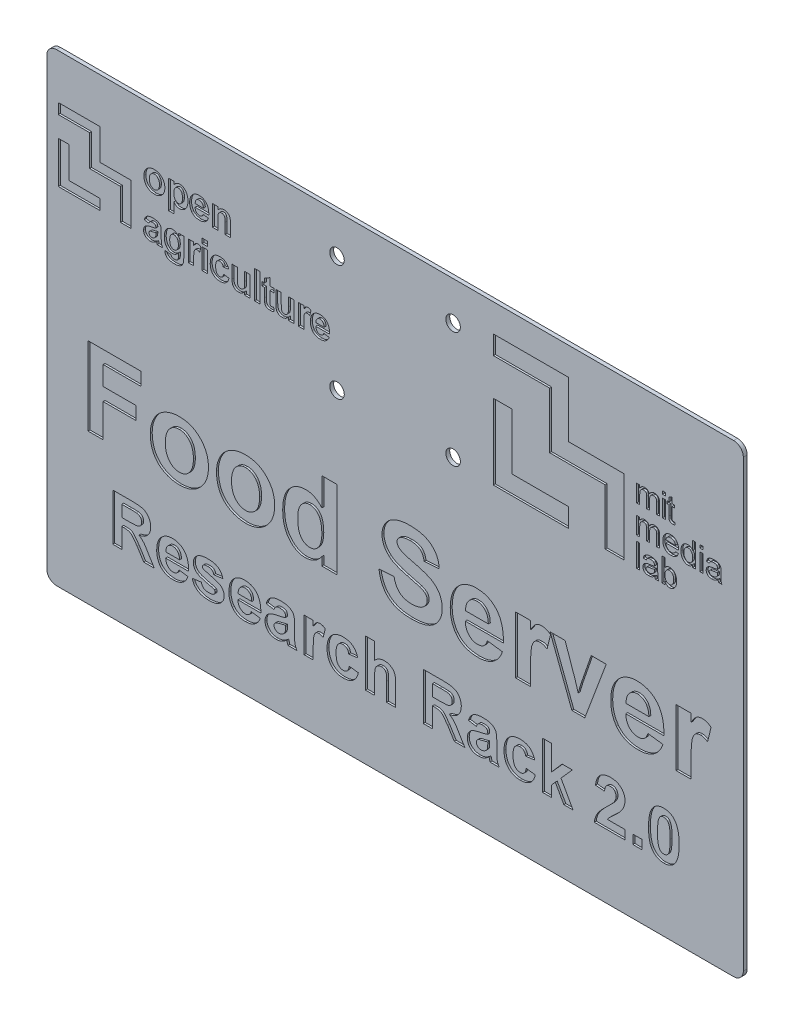
SolidWorks part; units mm, degrees
ref_plane "Front" through (0, 0, 0) normal (0, 0, 1) x (1, 0, 0)
ref_plane "Top" through (0, 0, 0) normal (0, 1, 0) x (1, 0, 0)
ref_plane "Right" through (0, 0, 0) normal (1, 0, 0) x (0, 0, -1)
sketch "Sketch1" plane through (0, 0, 0) normal (0, 0, 1) x (1, 0, 0)
  line L0 (0, 0) -> (0, 88.9) construction
  line L1 (-228.6, 152.4) -> (228.6, 152.4)
  line L2 (-228.6, 152.4) -> (-228.6, -152.4)
  line L3 (-228.6, -152.4) -> (228.6, -152.4)
  line L4 (228.6, 152.4) -> (228.6, -152.4)
  line L5 (-228.6, 152.4) -> (228.6, -152.4) construction
  line L6 (-228.6, -152.4) -> (228.6, 152.4) construction
  line L8 (-38.1, 127) -> (38.1, 127) construction
  line L9 (-38.1, 127) -> (-38.1, 50.8) construction
  line L10 (-38.1, 50.8) -> (38.1, 50.8) construction
  line L11 (38.1, 127) -> (38.1, 50.8) construction
  line L12 (-38.1, 127) -> (38.1, 50.8) construction
  line L13 (-38.1, 50.8) -> (38.1, 127) construction
  circle A0 centre (38.1, 127) radius 4.7625
  circle A1 centre (38.1, 50.8) radius 4.7625
  circle A2 centre (-38.1, 50.8) radius 4.7625
  circle A3 centre (-38.1, 127) radius 4.7625
  point P0 (0, 0)
  point P16 (0, 85.676)
  dimension "D3" = 9.525
  dimension "D1" = 457.2
  dimension "D2" = 304.8
  dimension "D4" = 76.2
  dimension "D5" = 76.2
  dimension "D6" = 25.4
extrude "Boss-Extrude1" add sketch "Sketch1" along normal blind 2.54
sketch "Sketch2" plane through (0, 0, 2.54) normal (0, 0, 1) x (1, 0, 0)
  line L0 (-228.6, -110.3412) -> (228.6, -110.3412) construction
  line L1 (-228.6, 152.4) -> (-228.6, -152.4) construction
  line L2 (228.6, -152.4) -> (228.6, 152.4) construction
  line L3 (-228.6, -54.1215) -> (228.6, -54.1215) construction
  line L4 (0, 0) -> (0, 83.06) construction
  line L6 (64.5155, 134.119) -> (113.7506, 134.119)
  line L7 (113.7506, 134.119) -> (113.7506, 97.5418)
  line L8 (113.7506, 97.5418) -> (150.2405, 97.5418)
  line L9 (150.2405, 97.5418) -> (150.2405, 48.5217)
  line L10 (150.2405, 48.5217) -> (137.9317, 48.5217)
  line L11 (137.9317, 48.5217) -> (137.9317, 85.0584)
  line L12 (137.9317, 85.0584) -> (101.5292, 85.0584)
  line L13 (101.5292, 85.0584) -> (101.5292, 121.8102)
  line L14 (101.5292, 121.8102) -> (64.5155, 121.8102)
  line L15 (64.5155, 121.8102) -> (64.5155, 134.119)
  line L16 (64.5155, 97.5418) -> (76.9116, 97.5418)
  line L17 (76.9116, 97.5418) -> (76.9116, 60.6155)
  line L18 (76.9116, 60.6155) -> (113.7506, 60.6155)
  line L19 (113.7506, 60.6155) -> (113.7506, 48.2194)
  line L20 (113.7506, 48.2194) -> (64.5155, 48.2194)
  line L21 (64.5155, 48.2194) -> (64.5155, 97.5418)
  line L22 (157.2149, 85.0584) -> (225.8164, 85.0584) construction
  line L23 (157.2149, 66.7596) -> (220.6979, 66.7596) construction
  line L24 (157.2149, 47.8869) -> (195.1273, 47.8869) construction
  line L25 (-221.0468, 122.883) -> (-193.694, 122.883)
  line L26 (-193.694, 122.883) -> (-193.694, 102.5624)
  line L27 (-193.694, 102.5624) -> (-173.4218, 102.5624)
  line L28 (-173.4218, 102.5624) -> (-173.4218, 75.161)
  line L29 (-173.4218, 75.161) -> (-180.2601, 75.161)
  line L30 (-180.2601, 75.161) -> (-180.2601, 95.6272)
  line L31 (-180.2601, 95.6272) -> (-200.4837, 95.6272)
  line L32 (-200.4837, 95.6272) -> (-200.4837, 116.0448)
  line L33 (-200.4837, 116.0448) -> (-221.0468, 116.0448)
  line L34 (-221.0468, 116.0448) -> (-221.0468, 122.883)
  line L35 (-221.0468, 102.5624) -> (-214.1601, 102.5624)
  line L36 (-214.1601, 102.5624) -> (-214.1601, 82.0478)
  line L37 (-214.1601, 82.0478) -> (-193.694, 82.0478)
  line L38 (-193.694, 82.0478) -> (-193.694, 75.161)
  line L39 (-193.694, 75.161) -> (-221.0468, 75.161)
  line L40 (-221.0468, 75.161) -> (-221.0468, 102.5624)
  line L41 (-165.808, 102.5624) -> (-74.3812, 102.5624) construction
  line L42 (-165.808, 74.527) -> (0.0083, 74.527) construction
  text T0 "mit" font "Arial" height in points 60
  text T1 "media" font "Arial" height in points 60
  text T2 "lab" font "Arial" height in points 60
  text T3 "open" font "Arial" height in points 72
  text T4 "agriculture" font "Arial" height in points 72
  text T5 "Food Server" font "Arial" height in points 200
  text T6 "Research Rack 2.0" font "Arial" height in points 120
extrude "Cut-Extrude2" cut sketch "Sketch2" against normal blind 1.27
fillet "Fillet1" radius 6.35 4 edges at (228.6, 152.4, 1.27) (228.6, -152.4, 1.27) (-228.6, -152.4, 1.27) (-228.6, 152.4, 1.27)
